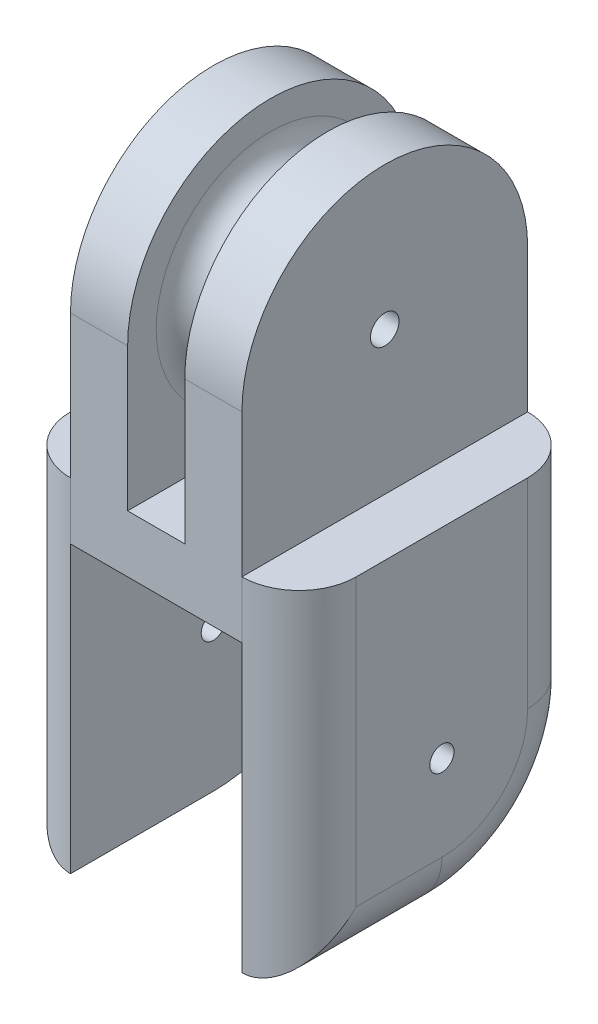
SolidWorks part; units mm, degrees
ref_plane "Front Plane" through (0, 0, 0) normal (0, 0, 1) x (1, 0, 0)
ref_plane "Top Plane" through (0, 0, 0) normal (0, 1, 0) x (1, 0, 0)
ref_plane "Right Plane" through (0, 0, 0) normal (1, 0, 0) x (0, 0, -1)
sketch "Sketch1" plane through (0, 0, 0) normal (0, 1, 0) x (1, 0, 0)
  line L0 (10, 10) -> (-10, -10) construction
  line L1 (-10, 10) -> (10, 10)
  line L2 (-10, 10) -> (-10, -10)
  line L3 (-10, -10) -> (10, -10)
  line L4 (10, 10) -> (10, -10)
  line L5 (-10, 10) -> (10, -10) construction
  point P5 (0, 0)
  dimension "D1" = 20
  dimension "D2" = 20
extrude "Boss-Extrude1" add sketch "Sketch1" along normal blind 4
sketch "Sketch4" plane through (0, 0, 0) normal (0, -1, 0) x (1, 0, 0)
  line L0 (10, -10) -> (-10, -10) construction
  line L1 (-10, 10) -> (-6, 10)
  line L2 (-10, 10) -> (-10, -10)
  line L3 (-10, -10) -> (-6, -10)
  line L4 (-6, 10) -> (-6, -10)
  line L5 (-10, 10) -> (10, 10) construction
  line L6 (10, -10) -> (6, -10)
  line L7 (10, -10) -> (10, 10)
  line L8 (10, 10) -> (6, 10)
  line L9 (6, -10) -> (6, 10)
  dimension "D1" = 4
  dimension "D2" = 4
extrude "Boss-Extrude2" add sketch "Sketch4" along normal blind 10
sketch "Sketch5" plane through (-10, 0, 0) normal (-1, 0, 0) x (0, 0, 1)
  line L0 (10, -10) -> (-10, -10) construction
  line L4 (0, -20) -> (10, -20)
  line L5 (10, -10) -> (10, -20)
  arc A0 (10, -10) -> (0, -20) centre (0, -10) ccw
extrude "Boss-Extrude3" add sketch "Sketch5" against normal blind 4
sketch "Sketch6" plane through (10, 0, 0) normal (1, 0, 0) x (0, 0, -1)
  line L0 (10, -10) -> (-10, -10) construction
  line L4 (0, -20) -> (-10, -20)
  line L5 (-10, -10) -> (-10, -20)
  arc A0 (0, -20) -> (-10, -10) centre (0, -10) ccw
extrude "Boss-Extrude4" add sketch "Sketch6" against normal blind 4
sketch "Sketch7" plane through (-10, 0, 0) normal (-1, 0, 0) x (0, 0, 1)
  circle A0 centre (0, -10) radius 0.85
  dimension "D1" = 1.7
extrude "Cut-Extrude1" cut sketch "Sketch7" against normal through all
fillet "Fillet1" radius 4 8 edges at (-10, -8, 10) (-10, -17.0711, -7.0711) (10, -8, 10) (10, -17.0711, -7.0711) (-10, -3, -10) (10, -3, -10) (10, -20, 5) (-10, -20, 5)
sketch "Sketch8" plane through (0, 4, 0) normal (0, 1, 0) x (1, 0, 0)
  line L0 (6, 10) -> (-6, 10) construction
  line L1 (6, -10) -> (2, -10)
  line L2 (6, -10) -> (6, 10)
  line L3 (6, 10) -> (2, 10)
  line L4 (2, -10) -> (2, 10)
  line L5 (-10, 6) -> (-10, -6) construction
  line L6 (-6, -10) -> (-2, -10)
  line L7 (-6, -10) -> (-6, 10)
  line L8 (-6, 10) -> (-2, 10)
  line L9 (-2, -10) -> (-2, 10)
  line L10 (10, -6) -> (10, 6) construction
  dimension "D1" = 4
  dimension "D2" = 4
  dimension "D3" = 4
  dimension "D4" = 4
extrude "Boss-Extrude5" add sketch "Sketch8" along normal blind 10
sketch "Sketch9" plane through (6, 0, 0) normal (1, 0, 0) x (0, 0, -1)
  line L0 (-10, 14) -> (10, 14) construction
  circle A0 centre (0, 14) radius 10
extrude "Boss-Extrude6" add sketch "Sketch9" against normal blind 4
sketch "Sketch10" plane through (-6, 0, 0) normal (-1, 0, 0) x (0, 0, 1)
  line L0 (-10, 14) -> (10, 14) construction
  circle A0 centre (0, 14) radius 10
extrude "Boss-Extrude7" add sketch "Sketch10" against normal blind 4
sketch "Sketch12" plane through (-6, 0, 0) normal (-1, 0, 0) x (0, 0, 1)
  circle A0 centre (0, 14) radius 1
  dimension "D1" = 2
extrude "Cut-Extrude2" cut sketch "Sketch12" against normal through all
sketch "Sketch13" plane through (-2, 0, 0) normal (1, 0, 0) x (0, 0, -1)
  circle A0 centre (0, 14) radius 6
  dimension "D1" = 12
sketch "Sketch14" plane through (-2, 0, 0) normal (1, 0, 0) x (0, 0, -1)
  circle A0 centre (0, 14) radius 3.5
  dimension "D1" = 7
extrude "Boss-Extrude8" add sketch "Sketch13" along normal blind 4
extrude "Cut-Extrude3" cut sketch "Sketch14" along normal blind 4
fillet "Fillet2" radius 2 2 edges at (2, 14, -6) (-2, 14, 6)
sketch "Sketch16" plane through (0, 0, 0) normal (0, -1, 0) x (1, 0, 0)
  line L0 (6, -10) -> (-6, -10) construction
  line L1 (-6, 0) -> (6, 0) construction
  line L2 (-6, -10) -> (-6, 10) construction
  line L3 (6, 10) -> (6, -10) construction
  circle A0 centre (0, -6) radius 0.5
  circle A1 centre (0, 6) radius 0.5
  dimension "D1" = 1
  dimension "D2" = 4
extrude "Cut-Extrude4" cut sketch "Sketch16" against normal up to next
